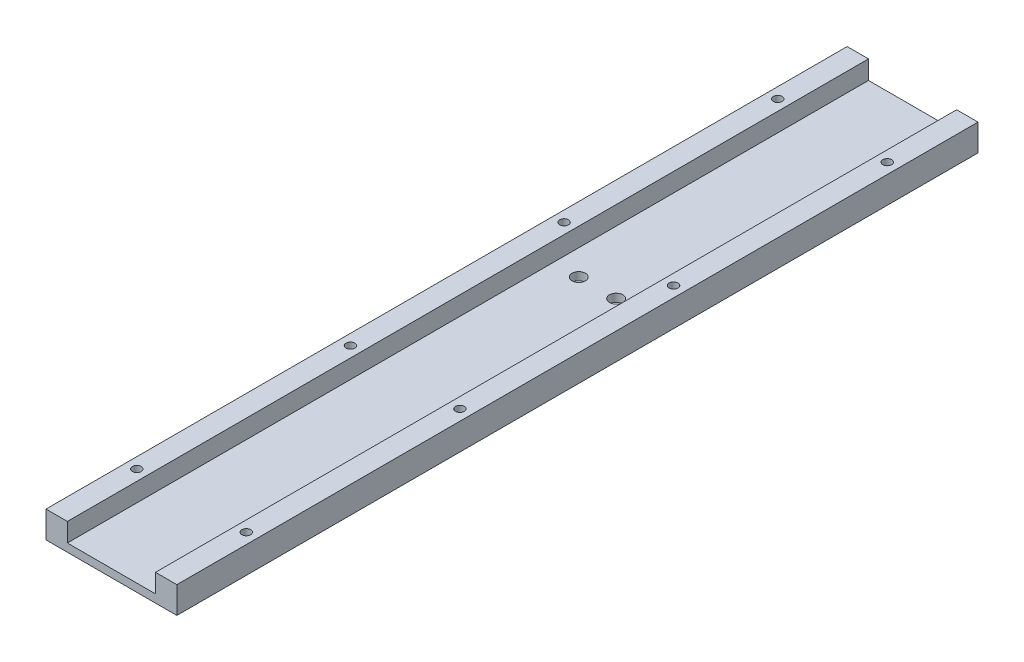
SolidWorks part; units mm, degrees
other "Objet de détail1"
ref_plane "Front" through (0, 0, 0) normal (0, 0, 1) x (1, 0, 0)
ref_plane "Top" through (0, 0, 0) normal (0, 1, 0) x (1, 0, 0)
ref_plane "Right" through (0, 0, 0) normal (1, 0, 0) x (0, 0, -1)
sketch "Esquisse1" plane through (0, 0, 0) normal (0, 0, 1) x (1, 0, 0)
  line L0 (0, 0) -> (0, 10)
  line L1 (0, 10) -> (8, 10)
  line L2 (49, 10) -> (41, 10)
  line L4 (8, 10) -> (8, 3)
  line L5 (8, 3) -> (41, 3)
  line L6 (0, 0) -> (49, 0)
  line L7 (24.5, 0) -> (24.5, 3) construction
  line L8 (41, 10) -> (41, 3)
  line L12 (49, 0) -> (49, 10)
  dimension "D1" = 33
  dimension "D2" = 3
  dimension "D3" = 8
  dimension "D4" = 10
extrude "Boss.-Extru.1" add sketch "Esquisse1" along normal blind 300
sketch "Esquisse2" plane through (0, 3, 0) normal (0, 1, 0) x (1, 0, 0)
  line L0 (24.5, -300) -> (24.5, -118) construction
  line L1 (41, -300) -> (8, -300) construction
  line L2 (24.5, -118) -> (17.5, -118) construction
  circle A0 centre (17.5, -118) radius 2.5
  circle A1 centre (31.5, -118) radius 2.5
  dimension "D1" = 5
  dimension "D2" = 14
  dimension "D3" = 182
extrude "Enlèv. mat.-Extru.1" cut sketch "Esquisse2" against normal through all both and the other way through all
sketch "Esquisse3" plane through (0, 10, 0) normal (0, 1, 0) x (1, 0, 0)
  line L0 (45, -300) -> (45, 0) construction
  line L1 (49, -300) -> (41, -300) construction
  line L2 (49, 0) -> (41, 0) construction
  line L3 (45, -150) -> (49, -150) construction
  line L4 (49, -300) -> (49, 0) construction
  line L5 (24.5, -300) -> (24.5, 0) construction
  line L6 (41, -300) -> (8, -300) construction
  line L7 (41, 0) -> (8, 0) construction
  line L8 (4, -150) -> (0, -150) construction
  circle A0 centre (45, -270) radius 1.65
  circle A1 centre (45, -190) radius 1.65
  circle A2 centre (45, -110) radius 1.65
  circle A3 centre (45, -30) radius 1.65
  circle A4 centre (4, -30) radius 1.65
  circle A5 centre (4, -110) radius 1.65
  circle A6 centre (4, -190) radius 1.65
  circle A7 centre (4, -270) radius 1.65
  dimension "D3" = 3.3
  dimension "D1" = 80
  dimension "D2" = 40
extrude "Enlèv. mat.-Extru.2" cut sketch "Esquisse3" against normal through all both and the other way through all
